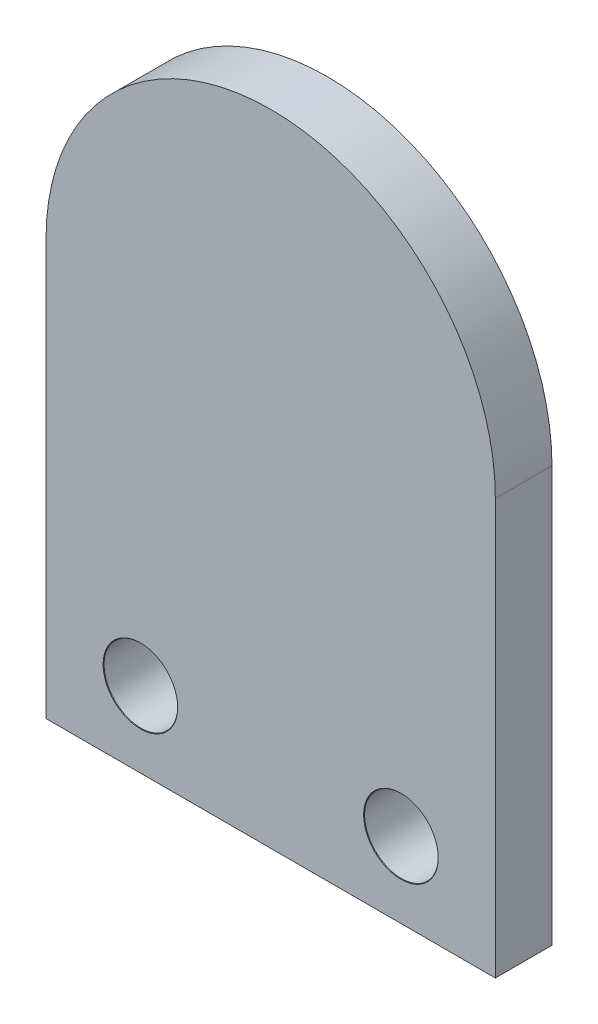
SolidWorks part; units mm, degrees
ref_plane "Front Plane" through (0, 0, 0) normal (0, 0, 1) x (1, 0, 0)
ref_plane "Top Plane" through (0, 0, 0) normal (0, 1, 0) x (1, 0, 0)
ref_plane "Right Plane" through (0, 0, 0) normal (1, 0, 0) x (0, 0, -1)
sketch "Sketch1" plane through (0, 0, 0) normal (0, 0, 1) x (1, 0, 0)
  line L0 (-11.9, 0) -> (-11.9, -22)
  line L1 (-11.9, -22) -> (11.9, -22)
  line L2 (11.9, -22) -> (11.9, 0)
  arc A0 (11.9, 0) -> (-11.9, 0) centre (0, 0) ccw
  dimension "D1" = 22
  dimension "D2" = 23.8
extrude "Boss-Extrude1" add sketch "Sketch1" along normal blind 3
sketch "Sketch2" plane through (0, 0, 0) normal (0, 0, -1) x (-1, 0, 0)
  circle A0 centre (0, 0) radius 6 construction
  circle A1 centre (0, 6) radius 1.95
  circle A2 centre (6, 0) radius 1.95
  circle A3 centre (0, -6) radius 1.95
  circle A4 centre (-6, 0) radius 1.95
  point P14 (0, 0)
  dimension "D1" = 12
  dimension "D2" = 3.9
  dimension "D3" = 4
extrude "Boss-Extrude2" add sketch "Sketch2" along normal blind 3
hole_wizard "M3.5 Clearance Hole1" positions "Sketch3" profile "Sketch4" hole size "M3.5" standard "ANSI Metric" end condition through all
sketch "Sketch3" plane through (0, 0, 3) normal (0, 0, 1) x (1, 0, 0)
  line L0 (-11.9, -22) -> (11.9, -22) construction
  line L1 (0, -22) -> (0, 14.1608) construction
  line L3 (-11.9, 0) -> (-11.9, -22) construction
  point P0 (6.9, -18)
  point P3 (-6.9, -18)
  dimension "D1" = 5
  dimension "D2" = 4
  dimension "D3" = 6.9
sketch "Sketch4" plane through (6.9, -18, 3) normal (1, 0, 0) x (0, -1, 0)
  line L0 (0, 0) -> (0, 6)
  line L1 (0, 6) -> (1.95, 6)
  line L2 (1.95, 6) -> (1.95, 0.025)
  line L3 (1.95, 0.025) -> (1.975, 0)
  line L5 (1.975, 0) -> (0, 0)
  line L6 (-1.95, 0.025) -> (-1.975, 0) construction
  line L11 (0, -6.35) -> (0, 107.95) construction
  dimension "Thru Hole Dia." = 3.9
  dimension "Thru Hole Depth" = 6
  dimension "Near C'Sink Dia." = 3.95
  dimension "Near C'Sink Angle" = 90
